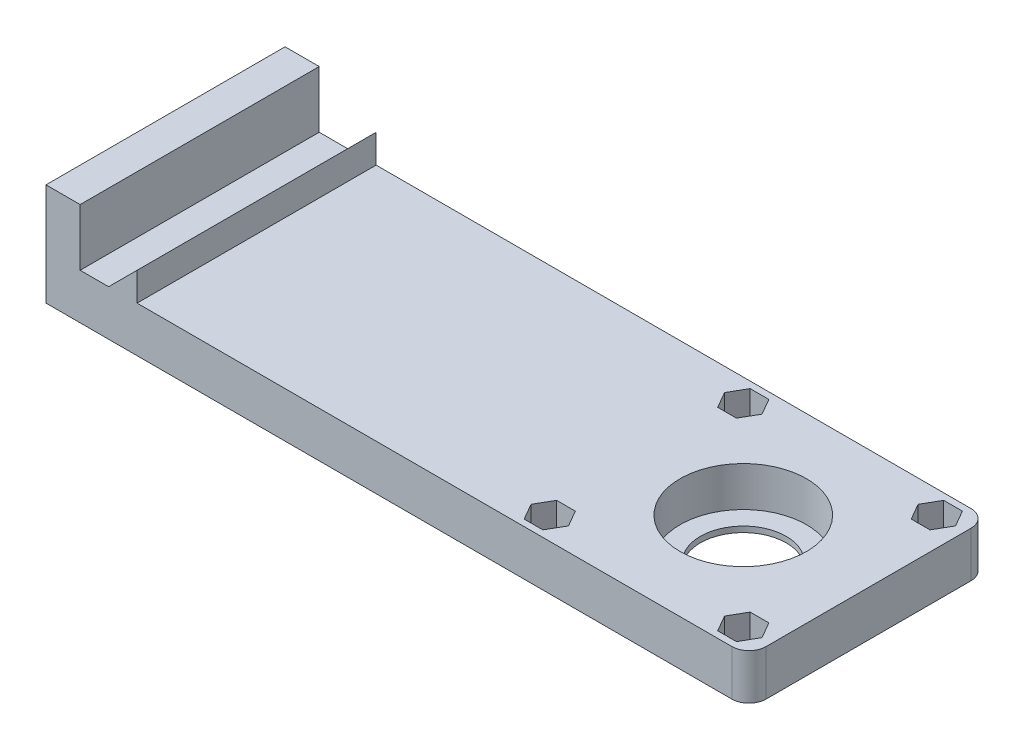
SolidWorks part; units mm, degrees
ref_plane "Front Plane" through (0, 0, 0) normal (0, 0, 1) x (1, 0, 0)
ref_plane "Top Plane" through (0, 0, 0) normal (0, 1, 0) x (1, 0, 0)
ref_plane "Right Plane" through (0, 0, 0) normal (1, 0, 0) x (0, 0, -1)
sketch "Sketch1" plane through (0, 0, 0) normal (0, 1, 0) x (1, 0, 0)
  line L1 (-61.75, -21) -> (61.75, -21)
  line L2 (-61.75, -21) -> (-61.75, 21)
  line L3 (-61.75, 21) -> (61.75, 21)
  line L4 (61.75, -21) -> (61.75, 21)
  line L5 (-61.75, -21) -> (61.75, 21) construction
  line L6 (-61.75, 21) -> (61.75, -21) construction
  point P0 (0, 0)
  dimension "D1" = 123.5
  dimension "D2" = 42
extrude "Boss-Extrude1" add sketch "Sketch1" along normal blind 8
sketch "Sketch2" plane through (0, 8, 0) normal (0, 1, 0) x (1, 0, 0)
  line L0 (61.75, 0) -> (39.75, 0) construction
  line L1 (61.75, -21) -> (61.75, 21) construction
  circle A0 centre (39.75, 0) radius 11.1
  dimension "D2" = 22.2
  dimension "D1" = 22
extrude "Cut-Extrude1" cut sketch "Sketch2" against normal blind 7
sketch "Sketch3" plane through (0, 0, 0) normal (0, -1, 0) x (1, 0, 0)
  line L0 (61.75, 0) -> (39.75, 0) construction
  line L1 (61.75, 21) -> (61.75, -21) construction
  circle A0 centre (39.75, 0) radius 7.55
  dimension "D2" = 15.1
  dimension "D1" = 22
extrude "Cut-Extrude2" cut sketch "Sketch3" against normal up to next
sketch "Sketch9" plane through (0, 8, 0) normal (0, 1, 0) x (1, 0, 0)
  line L0 (56.75, 21) -> (56.75, 17) construction
  line L1 (61.75, 21) -> (-61.75, 21) construction
  line L2 (56.75, 17) -> (61.75, 17) construction
  line L3 (61.75, -21) -> (61.75, 21) construction
  line L4 (61.75, 0) -> (39.75, 0) construction
  line L5 (39.75, 0) -> (39.75, 21) construction
  line L6 (61.75, 21) -> (-61.75, 21) construction
  line L7 (58.3954, 19.85) -> (55.1046, 19.85)
  line L8 (55.1046, 19.85) -> (53.4591, 17)
  line L9 (53.4591, 17) -> (55.1046, 14.15)
  line L10 (55.1046, 14.15) -> (58.3954, 14.15)
  line L11 (58.3954, 14.15) -> (60.0409, 17)
  line L12 (60.0409, 17) -> (58.3954, 19.85)
  line L13 (60.0409, -17) -> (58.3954, -19.85)
  line L14 (58.3954, -19.85) -> (55.1046, -19.85)
  line L15 (55.1046, -19.85) -> (53.4591, -17)
  line L16 (53.4591, -17) -> (55.1046, -14.15)
  line L17 (55.1046, -14.15) -> (58.3954, -14.15)
  line L18 (58.3954, -14.15) -> (60.0409, -17)
  line L19 (19.4591, 17) -> (21.1046, 19.85)
  line L20 (21.1046, 19.85) -> (24.3954, 19.85)
  line L21 (24.3954, 19.85) -> (26.0409, 17)
  line L22 (26.0409, 17) -> (24.3954, 14.15)
  line L23 (24.3954, 14.15) -> (21.1046, 14.15)
  line L24 (21.1046, 14.15) -> (19.4591, 17)
  line L25 (21.1046, -14.15) -> (19.4591, -17)
  line L26 (24.3954, -14.15) -> (21.1046, -14.15)
  line L27 (26.0409, -17) -> (24.3954, -14.15)
  line L28 (24.3954, -19.85) -> (26.0409, -17)
  line L29 (21.1046, -19.85) -> (24.3954, -19.85)
  line L30 (19.4591, -17) -> (21.1046, -19.85)
  circle A7 centre (56.75, 17) radius 2.85 construction
  point P4 (59.2182, 15.575)
  dimension "D3" = 5.7
  dimension "D1" = 4
  dimension "D2" = 5
  dimension "D4" = 0
extrude "Cut-Extrude4" cut sketch "Sketch9" against normal blind 6
sketch "Sketch10" plane through (0, 0, 0) normal (0, -1, 0) x (1, 0, 0)
  line L0 (56.75, 21) -> (56.75, 17) construction
  line L1 (-61.75, 21) -> (61.75, 21) construction
  line L2 (56.75, 17) -> (61.75, 17) construction
  line L3 (61.75, 21) -> (61.75, -21) construction
  line L4 (39.75, 0) -> (39.75, 21) construction
  line L23 (39.75, 0) -> (61.75, 0) construction
  circle A1 centre (56.75, 17) radius 1.75
  circle A3 centre (22.75, 17) radius 1.75
  circle A4 centre (56.75, -17) radius 1.75
  circle A5 centre (22.75, -17) radius 1.75
  dimension "D3" = 3.5
  dimension "D1" = 4
  dimension "D2" = 5
extrude "Cut-Extrude5" cut sketch "Sketch10" against normal blind 2
sketch "Sketch12" plane through (0, 0, -21) normal (0, 0, -1) x (-1, 0, 0)
  line L0 (55.75, 8) -> (50.75, 8) construction
  line L1 (61.75, 8) -> (55.75, 8)
  line L2 (61.75, 8) -> (61.75, 18)
  line L3 (61.75, 18) -> (55.75, 18)
  line L4 (55.75, 8) -> (55.75, 18)
  line L5 (-61.75, 8) -> (61.75, 8) construction
  line L6 (50.75, 8) -> (45.75, 8)
  line L7 (45.75, 8) -> (45.75, 13)
  line L8 (45.75, 13) -> (50.75, 8)
  dimension "D1" = 10
  dimension "D2" = 6
  dimension "D3" = 5
  dimension "D4" = 5
  dimension "D5" = 5
extrude "Boss-Extrude2" add sketch "Sketch12" against normal up to surface (42 mm away) up to face at (0, 4, 21)
fillet "Fillet1" radius 3 2 edges at (61.75, 4, -21) (61.75, 4, 21)
